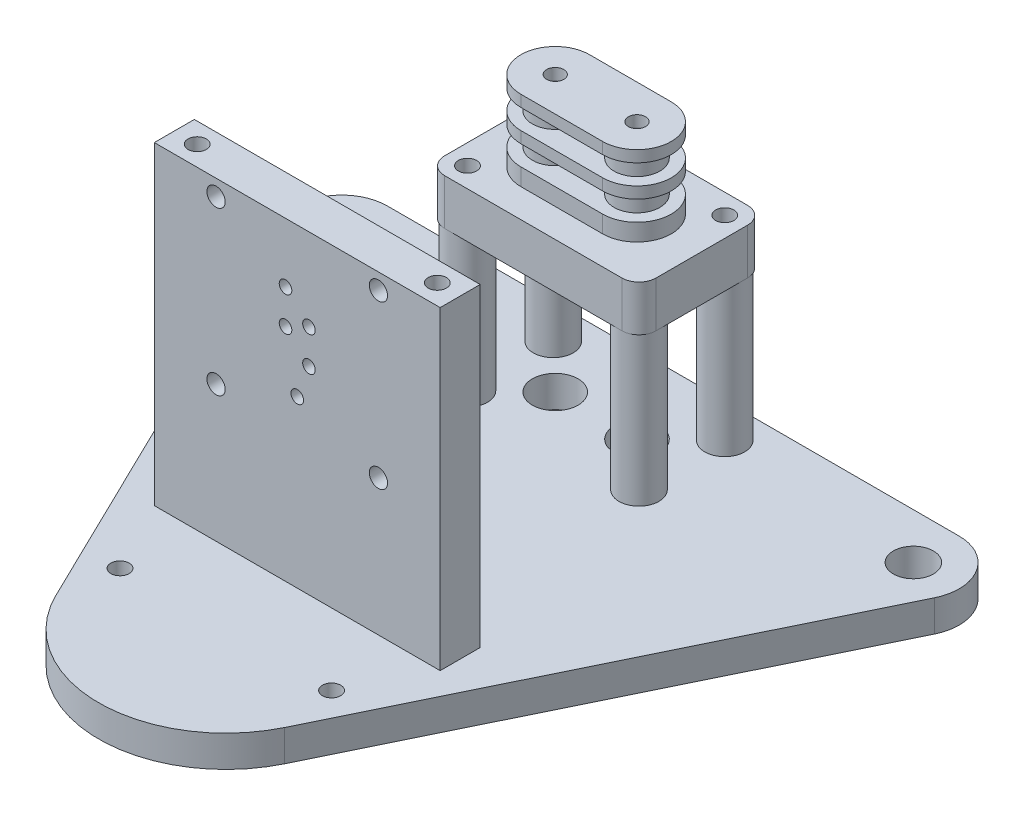
SolidWorks part; units mm, degrees
ref_plane "正面" through (0, 0, 0) normal (0, 0, 1) x (1, 0, 0)
ref_plane "平面" through (0, 0, 0) normal (0, 1, 0) x (1, 0, 0)
ref_plane "右側面" through (0, 0, 0) normal (1, 0, 0) x (0, 0, -1)
sketch "ｽｹｯﾁ1" plane through (0, 0, 0) normal (0, 1, 0) x (1, 0, 0)
  line L0 (0, -44) -> (0, 44) construction
  line L2 (-57.1947, 32.502) -> (-20, -44)
  line L3 (-20, -44) -> (20, -44) construction
  line L4 (57.1947, 32.502) -> (20, -44)
  line L7 (-50, 44) -> (50, 44)
  line L8 (0, 30.5) -> (-7.15, 30.5) construction
  line L9 (-3.15, 30.5) -> (-3.15, 44) construction
  line L10 (3.15, 30.5) -> (3.15, 44) construction
  line L11 (-50, 36) -> (0, 36) construction
  line L12 (-7.15, 34.5) -> (7.15, 34.5) construction
  line L13 (-10, 6.5) -> (0, 6.5) construction
  line L14 (-10, 8) -> (0, 8) construction
  circle A0 centre (-50, 36) radius 3.5
  arc A1 (-50, 44) -> (-57.1947, 32.502) centre (-50, 36) ccw
  arc A2 (-57.1947, 32.502) -> (-50, 44) centre (-50, 36) ccw construction
  arc A3 (57.1947, 32.502) -> (50, 44) centre (50, 36) cw construction
  arc A4 (50, 44) -> (57.1947, 32.502) centre (50, 36) cw
  circle A5 centre (50, 36) radius 3.5
  circle A6 centre (-7.15, 30.5) radius 4
  circle A7 centre (-7.15, 30.5) radius 1.5 construction
  circle A8 centre (7.15, 30.5) radius 4
  circle A9 centre (7.15, 30.5) radius 1.5 construction
  circle A10 centre (-10, 2.5) radius 1.5
  circle A11 centre (-10, 2.5) radius 4 construction
  arc A12 (-20, -44) -> (20, -44) centre (0, -34.2761) ccw
  point P15 (0, 0)
  dimension "D1" = 7
  dimension "D2" = 16
  dimension "D5" = 3
  dimension "D6" = 8
  dimension "D3" = 100
  dimension "D4" = 80
  dimension "D7" = 6.3
  dimension "D8" = 1.5
  dimension "D10" = 1.5
  dimension "D11" = 28
  dimension "10" = 10
  dimension "D9" = 40
extrude "ﾎﾞｽ - 押し出し1" add sketch "ｽｹｯﾁ1" along normal blind 5.5
sketch "ｽｹｯﾁ3" plane through (0, 5.5, 0) normal (0, 1, 0) x (1, 0, 0)
  circle A0 centre (-10, 2.5) radius 7.5
  circle A1 centre (-10, 2.5) radius 1.5 construction
  circle A2 centre (-10, 2.5) radius 1.5
  dimension "D1" = 15
extrude "ﾎﾞｽ - 押し出し2" add sketch "ｽｹｯﾁ3" along normal blind 23 separate body
sketch "ｽｹｯﾁ4" plane through (0, 28.5, 0) normal (0, 1, 0) x (1, 0, 0)
  circle A0 centre (-10, 2.5) radius 3
  circle A1 centre (-10, 2.5) radius 1.5 construction
  circle A2 centre (-10, 2.5) radius 1.5
  dimension "D1" = 6
extrude "ﾎﾞｽ - 押し出し3" add sketch "ｽｹｯﾁ4" along normal blind 3.5 separate body
sketch "ｽｹｯﾁ5" plane through (0, 28.5, 0) normal (0, 1, 0) x (1, 0, 0)
  circle A0 centre (-10, 2.5) radius 3.1
  circle A1 centre (-10, 2.5) radius 4
  dimension "D1" = 6.2
  dimension "D2" = 8
extrude "ﾎﾞｽ - 押し出し4" add sketch "ｽｹｯﾁ5" along normal blind 3 separate body
sketch "ｽｹｯﾁ6" plane through (0, 32, 0) normal (0, 1, 0) x (1, 0, 0)
  circle A0 centre (-10, 2.5) radius 1.5 construction
  circle A1 centre (-10, 2.5) radius 1.5
  circle A2 centre (-10, 2.5) radius 7.5
  dimension "D1" = 15
extrude "ﾎﾞｽ - 押し出し5" add sketch "ｽｹｯﾁ6" along normal blind 3 separate body
sketch "ｽｹｯﾁ7" plane through (0, 5.5, 0) normal (0, 1, 0) x (1, 0, 0)
  line L5 (15, 23) -> (-15, 23) construction
  line L6 (15, 23) -> (15, 38) construction
  line L7 (15, 38) -> (-15, 38) construction
  line L8 (-15, 23) -> (-15, 38) construction
  line L9 (15, 23) -> (-15, 38) construction
  line L10 (15, 38) -> (-15, 23) construction
  circle A8 centre (-15, 38) radius 1.6
  circle A9 centre (-15, 23) radius 1.6
  circle A10 centre (15, 23) radius 1.6
  circle A11 centre (15, 38) radius 1.6
  circle A12 centre (-15, 38) radius 3.5
  circle A13 centre (-15, 23) radius 3.5
  circle A14 centre (15, 38) radius 3.5
  circle A15 centre (15, 23) radius 3.5
  point P0 (0, 30.5)
  dimension "D1" = 30
  dimension "D2" = 15
  dimension "D3" = 3.2
  dimension "D4" = 7
extrude "ﾎﾞｽ - 押し出し6" add sketch "ｽｹｯﾁ7" along normal blind 26.1 separate body
sketch "ｽｹｯﾁ8" plane through (0, 5.5, 0) normal (0, 1, 0) x (1, 0, 0)
  circle A0 centre (15, 38) radius 1.6 construction
  circle A1 centre (15, 23) radius 1.6 construction
  circle A3 centre (-15, 23) radius 1.6 construction
  circle A4 centre (-15, 38) radius 1.6 construction
  circle A5 centre (15, 38) radius 1.6
  circle A6 centre (-15, 23) radius 1.6
  circle A7 centre (-15, 38) radius 1.6
  circle A8 centre (15, 23) radius 1.6
extrude "ｶｯﾄ - 押し出し1" cut sketch "ｽｹｯﾁ8" against normal through all
sketch "ｽｹｯﾁ9" plane through (0, 31.6, 0) normal (0, 1, 0) x (1, 0, 0)
  line L1 (15.5, 19.5) -> (-15.5, 19.5)
  line L2 (18.5, 22.5) -> (18.5, 38.5)
  line L3 (15.5, 41.5) -> (-15.5, 41.5)
  line L4 (-18.5, 22.5) -> (-18.5, 38.5)
  line L5 (18.5, 19.5) -> (-18.5, 41.5) construction
  line L6 (18.5, 41.5) -> (-18.5, 19.5) construction
  circle A0 centre (-15, 38) radius 1.6 construction
  circle A1 centre (-15, 23) radius 1.6 construction
  circle A2 centre (15, 38) radius 1.6 construction
  circle A3 centre (15, 38) radius 1.6
  circle A4 centre (-15, 23) radius 1.6
  circle A5 centre (-15, 38) radius 1.6
  circle A6 centre (-15, 38) radius 3.5 construction
  arc A7 (18.5, 38.5) -> (15.5, 41.5) centre (15.5, 38.5) ccw
  arc A8 (15.5, 19.5) -> (18.5, 22.5) centre (15.5, 22.5) ccw
  arc A9 (-15.5, 19.5) -> (-18.5, 22.5) centre (-15.5, 22.5) cw
  arc A10 (-15.5, 41.5) -> (-18.5, 38.5) centre (-15.5, 38.5) ccw
  circle A11 centre (7.15, 30.5) radius 1.5 construction
  circle A12 centre (-7.15, 30.5) radius 1.5 construction
  circle A13 centre (7.15, 30.5) radius 1.5
  circle A14 centre (-7.15, 30.5) radius 1.5
  point P0 (0, 30.5)
  dimension "D1" = 3
extrude "ﾎﾞｽ - 押し出し7" add sketch "ｽｹｯﾁ9" along normal blind 8
sketch "ｽｹｯﾁ10" plane through (0, 39.6, 0) normal (0, 1, 0) x (1, 0, 0)
  line L0 (-7.15, 30.5) -> (7.15, 30.5) construction
  line L1 (-7.15, 36.5) -> (7.15, 36.5)
  line L2 (-7.15, 24.5) -> (7.15, 24.5)
  arc A0 (-7.15, 36.5) -> (-7.15, 24.5) centre (-7.15, 30.5) ccw
  arc A1 (7.15, 24.5) -> (7.15, 36.5) centre (7.15, 30.5) ccw
  circle A2 centre (7.15, 30.5) radius 1.5 construction
  circle A3 centre (-7.15, 30.5) radius 1.5 construction
  circle A4 centre (7.15, 30.5) radius 1.5
  circle A5 centre (-7.15, 30.5) radius 1.5
  point P4 (0, 30.5)
  dimension "D1" = 6
extrude "ﾎﾞｽ - 押し出し9" add sketch "ｽｹｯﾁ10" along normal blind 3 separate body
sketch "ｽｹｯﾁ11" plane through (0, 42.6, 0) normal (0, 1, 0) x (1, 0, 0)
  circle A0 centre (7.15, 30.5) radius 1.5 construction
  circle A1 centre (-7.15, 30.5) radius 1.5 construction
  circle A2 centre (7.15, 30.5) radius 1.5
  circle A3 centre (-7.15, 30.5) radius 1.5
  circle A4 centre (-7.15, 30.5) radius 2.5
  circle A5 centre (7.15, 30.5) radius 2.5
  dimension "D1" = 5
extrude "ﾎﾞｽ - 押し出し10" add sketch "ｽｹｯﾁ11" along normal blind 3.5 separate body
sketch "ｽｹｯﾁ12" plane through (0, 42.6, 0) normal (0, 1, 0) x (1, 0, 0)
  circle A0 centre (-7.15, 30.5) radius 2.6
  circle A1 centre (-7.15, 30.5) radius 4 construction
  circle A2 centre (-7.15, 30.5) radius 4
  circle A3 centre (7.15, 30.5) radius 2.6
  circle A4 centre (7.15, 30.5) radius 4 construction
  circle A5 centre (7.15, 30.5) radius 4
  dimension "D1" = 5.2
extrude "ﾎﾞｽ - 押し出し11" add sketch "ｽｹｯﾁ12" along normal blind 3 separate body
sketch "ｽｹｯﾁ13" plane through (0, 46.1, 0) normal (0, 1, 0) x (1, 0, 0)
  line L2 (-7.15, 24.5) -> (7.15, 24.5)
  line L3 (7.15, 36.5) -> (-7.15, 36.5)
  line L4 (-7.15, 24.5) -> (7.15, 24.5)
  line L5 (7.15, 36.5) -> (-7.15, 36.5)
  circle A0 centre (7.15, 30.5) radius 1.5 construction
  circle A1 centre (-7.15, 30.5) radius 1.5 construction
  arc A2 (-7.15, 36.5) -> (-7.15, 24.5) centre (-7.15, 30.5) ccw
  arc A3 (7.15, 24.5) -> (7.15, 36.5) centre (7.15, 30.5) ccw
  arc A4 (-7.15, 36.5) -> (-7.15, 24.5) centre (-7.15, 30.5) ccw
  arc A5 (7.15, 24.5) -> (7.15, 36.5) centre (7.15, 30.5) ccw
  circle A6 centre (7.15, 30.5) radius 1.5
  circle A7 centre (-7.15, 30.5) radius 1.5
  dimension "D1" = 0
extrude "ﾎﾞｽ - 押し出し12" add sketch "ｽｹｯﾁ13" along normal blind 2 separate body
pattern_linear "直線ﾊﾟﾀｰﾝ1" count 2 spacing 5.5 along (0, 1, 0) of bodies 118 117 116 114 115
sketch "ｽｹｯﾁ15" plane through (0, 0, 0) normal (1, 0, 0) x (0, 0, -1)
  line L0 (-34.2761, 5.5) -> (-34.2761, 0) construction
  line L1 (-34.2761, 13) -> (-34.2761, -7)
  arc A0 (-34.2761, -7) -> (-34.2761, 13) centre (-34.2761, 3) cw
  point P0 (-34.2761, 0)
  dimension "D1" = 10
  dimension "D2" = 3
revolve "回転1" [suppressed] add sketch "ｽｹｯﾁ15" angle 360 about L1
sketch "ｽｹｯﾁ16" plane through (0, 0, 0) normal (0, -1, 0) x (1, 0, 0)
  circle A0 centre (0, 34.2761) radius 11
  dimension "D1" = 22
extrude "ｶｯﾄ - 押し出し2" [suppressed] cut sketch "ｽｹｯﾁ16" against normal blind 10
sketch "ｽｹｯﾁ18" plane through (0, 5.5, 0) normal (0, 1, 0) x (1, 0, 0)
  line L0 (12.5, -20.6618) -> (12.5, -47.8905) construction
  line L1 (14, -20.6618) -> (14, -47.8905)
  line L2 (11, -20.6618) -> (11, -47.8905)
  line L3 (10, -34.2761) -> (10, -42.3104) construction
  line L4 (17.5, -24.6618) -> (7.5, -24.6618) construction
  line L5 (17.5, -24.6618) -> (17.5, -27.6618) construction
  line L6 (17.5, -27.6618) -> (7.5, -27.6618) construction
  line L7 (7.5, -24.6618) -> (7.5, -27.6618) construction
  line L8 (17.5, -24.6618) -> (7.5, -27.6618) construction
  line L9 (17.5, -27.6618) -> (7.5, -24.6618) construction
  line L10 (11, -44.3905) -> (-11, -44.3905)
  line L12 (0, -3.025) -> (0, 3.025) construction
  line L13 (-12.5, -20.6618) -> (-12.5, -47.8905) construction
  line L14 (-14, -20.6618) -> (-14, -47.8905)
  line L15 (-11, -20.6618) -> (-11, -47.8905)
  line L16 (11, -24.1618) -> (-11, -24.1618)
  line L17 (0, -34.2761) -> (-12.5, -34.2761) construction
  circle A0 centre (0, -34.2761) radius 10 construction
  arc A1 (14, -20.6618) -> (11, -20.6618) centre (12.5, -20.6618) ccw
  arc A2 (11, -47.8905) -> (14, -47.8905) centre (12.5, -47.8905) ccw
  arc A3 (-14, -20.6618) -> (-11, -20.6618) centre (-12.5, -20.6618) cw
  arc A4 (-11, -47.8905) -> (-14, -47.8905) centre (-12.5, -47.8905) cw
  point P5 (12.5, -34.2761)
  point P11 (12.5, -26.1618)
  point P24 (-12.5, -34.2761)
  dimension "D1" = 20
  dimension "D2" = 10
  dimension "D3" = 3
  dimension "D4" = 4
  dimension "D5" = 1
  dimension "D6" = 3
  dimension "D7" = 0.5
extrude "ｶｯﾄ - 押し出し3" [suppressed] cut sketch "ｽｹｯﾁ18" against normal through all contours A4 L15 A3 L14 | L2 L16 L15 L10 | L2 A2 L1 A1
sketch "ｽｹｯﾁ19" plane through (0, 5.5, 0) normal (0, 1, 0) x (1, 0, 0)
  circle A0 centre (18.5, -34.2761) radius 1.6
  circle A1 centre (0, -34.2761) radius 18.5 construction
  circle A2 centre (-18.5, -34.2761) radius 1.6
  point P13 (0, -34.2761)
  dimension "D1" = 3.2
  dimension "D3" = 37
  dimension "D2" = 2
extrude "ｶｯﾄ - 押し出し4" cut sketch "ｽｹｯﾁ19" against normal up to surface (5.5 mm away) up to face at (15, 0, -36.4)
sketch "ｽｹｯﾁ20" plane through (0, 5.5, 0) normal (0, 1, 0) x (1, 0, 0)
  line L0 (0, -44) -> (0, 44) construction
  line L1 (25, -14.7761) -> (-25, -14.7761)
  line L2 (25, -14.7761) -> (25, -21.7761)
  line L3 (25, -21.7761) -> (-25, -21.7761)
  line L4 (-25, -14.7761) -> (-25, -21.7761)
  line L5 (25, -14.7761) -> (-25, -21.7761) construction
  line L6 (25, -21.7761) -> (-25, -14.7761) construction
  line L7 (-21, -18.2761) -> (21, -18.2761) construction
  circle A0 centre (0, -34.2761) radius 20.5 construction
  circle A1 centre (-21, -18.2761) radius 1.6
  circle A2 centre (21, -18.2761) radius 1.6
  point P3 (0, -18.2761)
  dimension "D1" = 41
  dimension "D4" = 3.2
  dimension "D2" = 7
  dimension "D3" = 50
  dimension "D5" = 4
  dimension "D6" = 16
extrude "ﾎﾞｽ - 押し出し13" add sketch "ｽｹｯﾁ20" along normal blind 55 separate body
sketch "ｽｹｯﾁ21" plane through (0, 5.5, 0) normal (0, -1, 0) x (1, 0, 0)
  line L0 (28, 24.7761) -> (-28, 24.7761)
  line L1 (-28, 24.7761) -> (-28, 11.7761)
  line L2 (-28, 11.7761) -> (28, 11.7761)
  line L3 (28, 11.7761) -> (28, 24.7761)
  line L4 (-25, 21.7761) -> (-25, 14.7761)
  line L5 (-25, 14.7761) -> (25, 14.7761)
  line L6 (25, 14.7761) -> (25, 21.7761)
  line L7 (25, 21.7761) -> (-25, 21.7761)
  line L8 (-25, 21.7761) -> (-25, 14.7761)
  line L9 (-25, 14.7761) -> (25, 14.7761)
  line L10 (25, 14.7761) -> (25, 21.7761)
  line L11 (25, 21.7761) -> (-25, 21.7761)
  dimension "D1" = 0
  dimension "D2" = 3
extrude "ﾎﾞｽ - 押し出し14" [suppressed] add sketch "ｽｹｯﾁ21" against normal blind 2
fillet "ﾌｨﾚｯﾄ2" [suppressed] radius 8
sketch "ｽｹｯﾁ22" plane through (0, 5.5, 0) normal (0, 1, 0) x (1, 0, 0)
  circle A0 centre (-21, -18.2761) radius 1.6
  circle A1 centre (21, -18.2761) radius 1.6
  circle A2 centre (21, -18.2761) radius 1.6 construction
extrude "ｶｯﾄ - 押し出し5" cut sketch "ｽｹｯﾁ22" against normal through all
sketch "ｽｹｯﾁ23" plane through (0, 0, 21.7761) normal (0, 0, 1) x (1, 0, 0)
  line L0 (3.15, 42.6) -> (11.15, 42.6) construction
  line L1 (-11.15, 42.6) -> (-3.15, 42.6) construction
  line L2 (11.15, 45.6) -> (3.15, 45.6) construction
  line L3 (-3.15, 45.6) -> (-11.15, 45.6) construction
  line L4 (11.15, 51.1) -> (3.15, 51.1) construction
  line L5 (3.15, 48.1) -> (11.15, 48.1) construction
  line L6 (-3.15, 51.1) -> (-11.15, 51.1) construction
  line L7 (-11.15, 48.1) -> (-3.15, 48.1) construction
  line L8 (3.15, 42.6) -> (11.15, 42.6) construction
  line L9 (-11.15, 42.6) -> (-3.15, 42.6) construction
  line L10 (11.15, 45.6) -> (3.15, 45.6) construction
  line L11 (-3.15, 45.6) -> (-11.15, 45.6) construction
  line L12 (11.15, 51.1) -> (3.15, 51.1) construction
  line L13 (3.15, 48.1) -> (11.15, 48.1) construction
  line L14 (-3.15, 51.1) -> (-11.15, 51.1) construction
  line L15 (-11.15, 48.1) -> (-3.15, 48.1) construction
  line L16 (-6, 31.5) -> (-14, 31.5) construction
  line L17 (-14, 28.5) -> (-6, 28.5) construction
  line L18 (-6, 31.5) -> (-14, 31.5) construction
  line L19 (-14, 28.5) -> (-6, 28.5) construction
  line L20 (-11.15, 51.1) -> (-11.15, 48.1) construction
  line L21 (-11.15, 45.6) -> (-11.15, 42.6) construction
  line L22 (-3.15, 42.6) -> (-3.15, 45.6) construction
  line L23 (-3.15, 48.1) -> (-3.15, 51.1) construction
  line L24 (3.15, 51.1) -> (3.15, 48.1) construction
  line L25 (3.15, 45.6) -> (3.15, 42.6) construction
  line L26 (-6, 31.5) -> (-6, 28.5) construction
  line L27 (-14, 31.5) -> (-14, 28.5) construction
  line L28 (11.15, 51.1) -> (11.15, 48.1) construction
  line L29 (11.15, 45.6) -> (11.15, 42.6) construction
  line L30 (0, 60.5) -> (0, 34.0276) construction
  line L31 (-25, 60.5) -> (25, 60.5) construction
  line L32 (-2.05, 50.1) -> (2.05, 46.1) construction
  circle A0 centre (-2.05, 50.1) radius 1.1
  circle A1 centre (2.05, 46.1) radius 1.1
  circle A4 centre (0, 34.5) radius 1.1
  circle A5 centre (-2.05, 44.1) radius 1.1
  circle A6 centre (2.05, 40.1) radius 1.1
  point P24 (0, 48.1)
  dimension "D1" = 2.2
  dimension "D3" = 6
  dimension "D4" = 1
  dimension "D5" = 2
  dimension "D6" = 3
  dimension "D2" = 2
extrude "ｶｯﾄ - 押し出し6" cut sketch "ｽｹｯﾁ23" against normal up to surface (7 mm away) up to face at (0, 33, 14.7761)
sketch "ｽｹｯﾁ24" plane through (0, 0, 21.7761) normal (0, 0, 1) x (1, 0, 0)
  line L1 (14.2, 29.3) -> (-14.2, 29.3) construction
  line L2 (14.2, 29.3) -> (14.2, 57.7) construction
  line L3 (14.2, 57.7) -> (-14.2, 57.7) construction
  line L4 (-14.2, 29.3) -> (-14.2, 57.7) construction
  line L5 (14.2, 29.3) -> (-14.2, 57.7) construction
  line L6 (14.2, 57.7) -> (-14.2, 29.3) construction
  line L7 (0, 60.5) -> (0, 34.0276) construction
  circle A0 centre (14.2, 57.7) radius 1.6
  circle A1 centre (-14.2, 57.7) radius 1.6
  circle A2 centre (-14.2, 29.3) radius 1.6
  circle A3 centre (14.2, 29.3) radius 1.6
  point P0 (0, 43.5)
  dimension "D3" = 3.2
  dimension "D1" = 28.4
  dimension "D2" = 0.6
extrude "ｶｯﾄ - 押し出し7" cut sketch "ｽｹｯﾁ24" against normal up to surface (7 mm away) up to face at (-0.95, 50.1, 14.7761)
